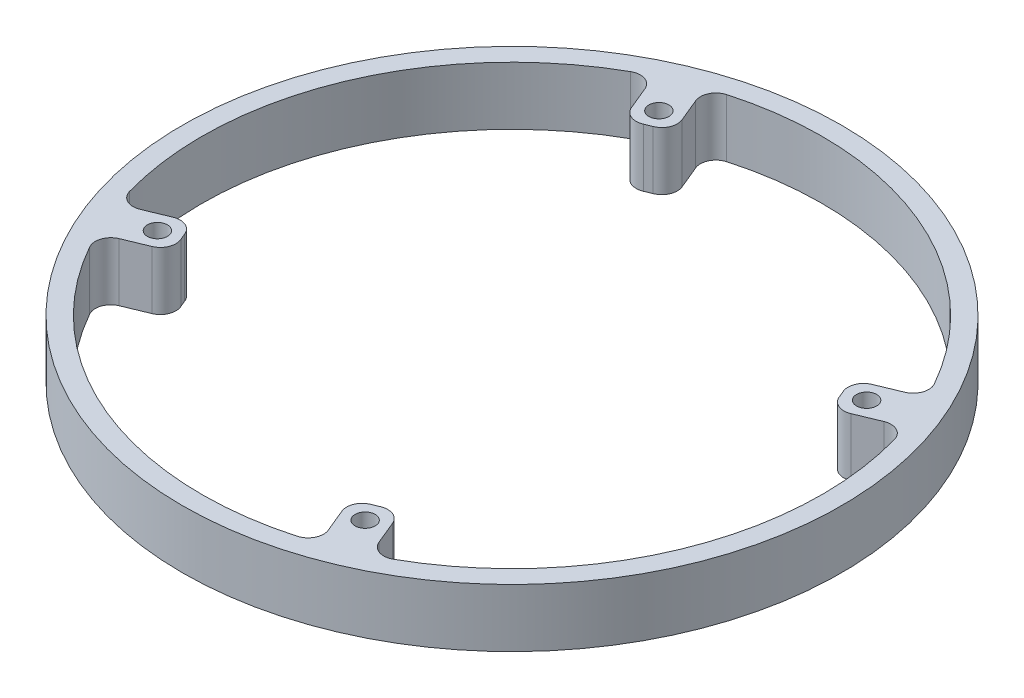
SolidWorks part; units mm, degrees
ref_plane "Front Plane" through (0, 0, 0) normal (0, 0, 1) x (1, 0, 0)
ref_plane "Top Plane" through (0, 0, 0) normal (0, 1, 0) x (1, 0, 0)
ref_plane "Right Plane" through (0, 0, 0) normal (1, 0, 0) x (0, 0, -1)
sketch "Sketch2" plane through (0, 0, 0) normal (1, 0, 0) x (0, 0, -1)
  line L0 (-65, 0) -> (-84.9998, 0)
  line L1 (-84.9998, 0) -> (-84.9998, 15)
  line L2 (-84.9998, 15) -> (-65, 15)
  line L5 (-65, 15) -> (-65, 0)
  dimension "D1" = 84.9998
  dimension "D2" = 15
  dimension "D3" = 65
ref_axis "Axis1" through (0, -0.75, 0) along (0, 1, 0)
revolve "Revolve1" add sketch "Sketch2" angle 360 about axis through (0, -0.75, 0) along (0, 1, 0)
hole_wizard "#6 (0.204) Diameter Hole1" positions "Sketch6" profile "Sketch7" hole size "#6" standard "ANSI Inch" end condition through all
sketch "Sketch6" plane through (0, 15, 0) normal (0, 1, 0) x (1, 0, 0)
  line L0 (0, 0) -> (-53.438, 129.0108) construction
  line L2 (0, 0) -> (0, 109.0908) construction
  point P0 (-26.7878, 64.6716)
  dimension "D1" = 22.5
  dimension "D2" = 70
sketch "Sketch7" plane through (-26.7878, 15, -64.6716) normal (1, 0, 0) x (0, 0, 1)
  line L0 (0, 0) -> (0, 15)
  line L1 (0, 15) -> (2.5908, 15)
  line L2 (2.5908, 15) -> (2.5908, 0)
  line L5 (2.5908, 0) -> (0, 0)
  line L11 (0, -6.35) -> (0, 107.95) construction
  dimension "Thru Hole Dia." = 5.1816
  dimension "Thru Hole Depth" = 15
pattern_circular "CirPattern3" count 4 over 360 about axis through (0, -0.75, 0) along (0, 1, 0) of "#6 (0.204) Diameter Hole1"
sketch "Sketch8" plane through (0, 15, 0) normal (0, 1, 0) x (1, 0, 0)
  line L0 (0, 0) -> (0, 111.8066) construction
  line L4 (0, 0) -> (35.0883, 84.7106) construction
  line L5 (0, 0) -> (113.8372, 0) construction
  line L6 (-4.7544, 24.5438) -> (-25.9354, 75.6791)
  line L7 (20.7169, 13.9932) -> (71.8523, 35.1742)
  line L8 (0, 0) -> (-26.7878, 64.6716) construction
  arc A0 (-4.7544, 24.5438) -> (20.7169, 13.9932) centre (0, 0) cw
  arc A1 (-25.9354, 75.6791) -> (71.8523, 35.1742) centre (0, 0) cw
  circle A2 centre (0, 0) radius 84.9998 construction
  dimension "D1" = 25
  dimension "D2" = 5
  dimension "D3" = 5
  dimension "D4" = 22.5
extrude "Cut-Extrude1" cut sketch "Sketch8" against normal through all
fillet "Fillet1" radius 4 4 edges at (71.8523, 7.5, -35.1742) (-25.9354, 7.5, -75.6791) (57.9608, 7.5, -29.4201) (-20.1813, 7.5, -61.7877)
pattern_circular "CirPattern4" count 4 over 360 about axis through (0, -0.75, 0) along (0, 1, 0) of "Cut-Extrude1", "Fillet1"
